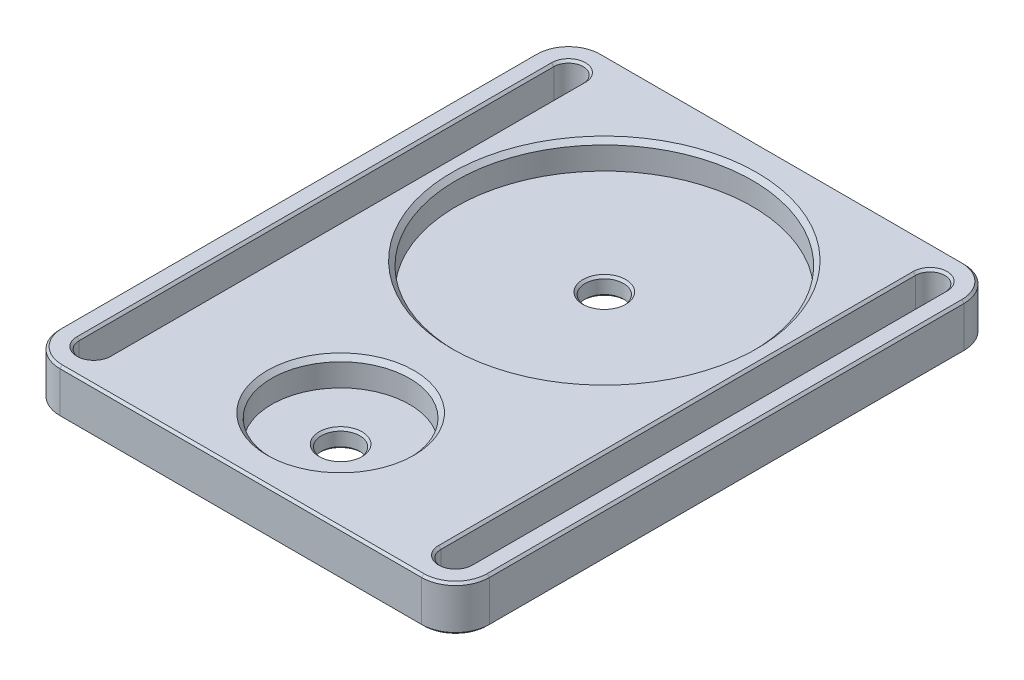
SolidWorks part; units mm, degrees
material "6061-T6 Aluminum"
ref_plane "Front Plane" through (0, 0, 0) normal (0, 0, 1) x (1, 0, 0)
ref_plane "Top Plane" through (0, 0, 0) normal (0, 1, 0) x (1, 0, 0)
ref_plane "Right Plane" through (0, 0, 0) normal (1, 0, 0) x (0, 0, -1)
sketch "Sketch1" plane through (0, 0, 0) normal (0, 1, 0) x (1, 0, 0)
  line L0 (0, 39.58) -> (0, 32.75) construction
  line L1 (-40, -80.42) -> (40, -80.42)
  line L2 (-47.5, -72.92) -> (-47.5, 32.08)
  line L3 (-40, 39.58) -> (40, 39.58)
  line L4 (47.5, -72.92) -> (47.5, 32.08)
  line L5 (0, -73.59) -> (0, -80.42) construction
  line L6 (-40, 32.08) -> (-40, -72.92) construction
  line L7 (-36.75, 32.08) -> (-36.75, -72.92)
  line L8 (-43.25, 32.08) -> (-43.25, -72.92)
  line L9 (40, 32.08) -> (40, -72.92) construction
  line L10 (43.25, 32.08) -> (43.25, -72.92)
  line L11 (36.75, 32.08) -> (36.75, -72.92)
  line L12 (-40, 0) -> (0, 0) construction
  line L13 (0, 0) -> (40, 0) construction
  line L14 (-40, -72.92) -> (-40, 32.08) construction
  line L15 (-46, -72.92) -> (-46, 32.08)
  line L16 (-34, -72.92) -> (-34, 32.08)
  line L17 (40, -72.92) -> (40, 32.08) construction
  line L18 (34, -72.92) -> (34, 32.08)
  line L19 (46, -72.92) -> (46, 32.08)
  circle A0 centre (0, 0) radius 32.75
  circle A1 centre (0, -58.34) radius 15.25
  arc A3 (-36.75, 32.08) -> (-43.25, 32.08) centre (-40, 32.08) ccw
  arc A4 (-43.25, -72.92) -> (-36.75, -72.92) centre (-40, -72.92) ccw
  arc A5 (43.25, 32.08) -> (36.75, 32.08) centre (40, 32.08) ccw
  arc A6 (36.75, -72.92) -> (43.25, -72.92) centre (40, -72.92) ccw
  circle A7 centre (0, 0) radius 4.25
  circle A8 centre (0, -58.34) radius 4.25
  arc A9 (-40, 39.58) -> (-47.5, 32.08) centre (-40, 32.08) ccw
  arc A11 (47.5, 32.08) -> (40, 39.58) centre (40, 32.08) ccw
  arc A12 (-47.5, -72.92) -> (-40, -80.42) centre (-40, -72.92) ccw
  arc A13 (40, -80.42) -> (47.5, -72.92) centre (40, -72.92) ccw
  arc A14 (-46, -72.92) -> (-34, -72.92) centre (-40, -72.92) ccw
  arc A15 (-34, 32.08) -> (-46, 32.08) centre (-40, 32.08) ccw
  arc A16 (34, -72.92) -> (46, -72.92) centre (40, -72.92) ccw
  arc A17 (46, 32.08) -> (34, 32.08) centre (40, 32.08) ccw
  point P0 (0, 0)
  point P2 (-40, -20.42)
  point P13 (0, 41.5825)
  point P17 (-40, -20.42)
  point P22 (40, -20.42)
  point P46 (40, -20.42)
  point P51 (-44, 33.0208)
  point P52 (0, 0)
  point P53 (-50, 43.8723)
  point P54 (-50, 40.587)
  dimension "D1" = 30.5
  dimension "D2" = 65.5
  dimension "D5" = 8.5
  dimension "D3" = 58.34
  dimension "D4" = 6.5
  dimension "D6" = 80
  dimension "D7" = 12
  dimension "D8" = 95
  dimension "D9" = 120
extrude "Boss-Extrude1" add sketch "Sketch1" along normal blind 10 contours L1 A13 L4 A11 L3 A9 L2 A12 A17 L19 A16 L18 A15 L16 A14 L15 A0 A1 | A0 A7 | A1 A8 | L11 A6 L10 A5 | L16 A15 L15 A14 A4 L8 A3 L7 | L19 A17 L18 A16 A6 L11 A5 L10 | L8 A4 L7 A3 | A7 | A8 region at (-45.1951, 0, 78.1151) region at (-40, 0, 20.42) region at (40, 0, 20.42) region at (-44.8239, 0, 20.42) region at (35.1761, 0, 20.42) region at (-31.8237, 0, 0) region at (-14.8187, 0, 58.34) region at (0, 0, 0) region at (0, 0, 58.34)
extrude "Cut-Extrude2" cut sketch "Sketch1<4>" along normal through all contours L11 A6 L10 A5 | A7 | A8 | L8 A4 L7 A3 region at (-40, 0, 20.42) region at (40, 0, 20.42) region at (0, 0, 0) region at (0, 0, 58.34)
sketch "Sketch1<4>" plane through (0, 0, 0) normal (0, 1, 0) x (1, 0, 0) same geometry as "Sketch1"
extrude "Cut-Extrude3" cut sketch "Sketch1<6>" along normal through all from offset 4 contours A0 A7 | A1 A8 region at (-31.8237, 0, 0) region at (-14.8187, 0, 58.34)
sketch "Sketch1<6>" plane through (0, 0, 0) normal (0, 1, 0) x (1, 0, 0) same geometry as "Sketch1"
chamfer "Chamfer1" distance 1 angle 45 2 edges at (0, 10, 73.59) (0, 10, 32.75)
chamfer "Chamfer2" distance 0.5 angle 45 36 edges at (0, 4, 62.59) (0, 0, 62.59) (0, 4, 4.25) (0, 0, 4.25) (43.25, 10, 20.42) (40, 10, -35.33) (40, 10, 76.17) (36.75, 10, 20.42) (43.25, 0, 20.42) (40, 0, -35.33) (40, 0, 76.17) (36.75, 0, 20.42) (-36.75, 10, 20.42) (-40, 10, -35.33) (-40, 10, 76.17) (-43.25, 10, 20.42) (-36.75, 0, 20.42) (-40, 0, -35.33) (-40, 0, 76.17) (-43.25, 0, 20.42) (0, 10, -39.58) (-45.3033, 10, -37.3833) (45.3033, 10, -37.3833) (-47.5, 10, 20.42) (47.5, 10, 20.42) (-45.3033, 10, 78.2233) (45.3033, 10, 78.2233) (0, 10, 80.42) (0, 0, -39.58) (-45.3033, 0, -37.3833) (45.3033, 0, -37.3833) (-47.5, 0, 20.42) (47.5, 0, 20.42) (-45.3033, 0, 78.2233) (45.3033, 0, 78.2233) (0, 0, 80.42)
